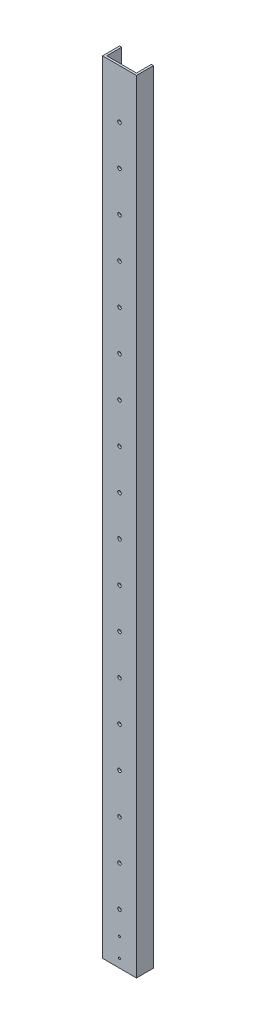
SolidWorks part; units mm, degrees
ref_plane "Front" through (0, 0, 0) normal (0, 0, 1) x (1, 0, 0)
ref_plane "Top" through (0, 0, 0) normal (0, 1, 0) x (1, 0, 0)
ref_plane "Right" through (0, 0, 0) normal (1, 0, 0) x (0, 0, -1)
sketch "Sketch1" plane through (0, 0, 0) normal (0, 1, 0) x (1, 0, 0)
  line L0 (3.175, 3.175) -> (3.175, 25.4)
  line L1 (0, 0) -> (50.8, 0)
  line L2 (0, 0) -> (0, 25.4)
  line L4 (50.8, 0) -> (50.8, 25.4)
  line L5 (3.175, 3.175) -> (47.625, 3.175)
  line L6 (47.625, 3.175) -> (47.625, 25.4)
  line L7 (0, 25.4) -> (3.175, 25.4)
  line L8 (50.8, 25.4) -> (47.625, 25.4)
  dimension "D1" = 25.4
  dimension "D2" = 50.8
  dimension "D3" = 3.175
extrude "Boss-Extrude1" add sketch "Sketch1" along normal blind 1168.4
sketch "Sketch2" plane through (0, 0, 0) normal (0, 0, 1) x (1, 0, 0)
  line L0 (25.4, 0) -> (25.4, 76.2) construction
  line L1 (0, 0) -> (50.8, 0) construction
  circle A0 centre (25.4, 76.2) radius 2.667
  circle A1 centre (25.4, 136.144) radius 2.667
  circle A2 centre (25.4, 196.088) radius 2.667
  circle A3 centre (25.4, 256.032) radius 2.667
  circle A4 centre (25.4, 315.976) radius 2.667
  circle A5 centre (25.4, 375.92) radius 2.667
  circle A6 centre (25.4, 435.864) radius 2.667
  circle A7 centre (25.4, 495.808) radius 2.667
  circle A8 centre (25.4, 555.752) radius 2.667
  circle A9 centre (25.4, 615.696) radius 2.667
  circle A10 centre (25.4, 675.64) radius 2.667
  circle A11 centre (25.4, 735.584) radius 2.667
  circle A12 centre (25.4, 795.528) radius 2.667
  circle A13 centre (25.4, 855.472) radius 2.667
  circle A14 centre (25.4, 915.416) radius 2.667
  circle A15 centre (25.4, 975.36) radius 2.667
  circle A16 centre (25.4, 1035.304) radius 2.667
  circle A17 centre (25.4, 1095.248) radius 2.667
  dimension "D2" = 5.334
  dimension "D1" = 76.2
  dimension "D3" = 18
extrude "Cut-Extrude1" cut sketch "Sketch2" against normal up to next
sketch "Sketch4" plane through (0, 0, 0) normal (0, 0, 1) x (1, 0, 0)
  line L0 (25.4, 41.275) -> (50.8, 41.275) construction
  line L1 (50.8, 1168.4) -> (50.8, 0) construction
  line L2 (25.4, 41.275) -> (0, 41.275) construction
  line L3 (0, 1168.4) -> (0, 0) construction
  line L4 (25.4, 41.275) -> (25.4, 12.7) construction
  line L5 (25.4, 12.7) -> (25.4, 0) construction
  line L6 (0, 0) -> (50.8, 0) construction
  circle A1 centre (25.4, 41.275) radius 1.5875
  circle A3 centre (25.4, 12.7) radius 1.5875
  dimension "D1" = 28.575
  dimension "D2" = 12.7
extrude "Cut-Extrude2" cut sketch "Sketch4" against normal up to next
ref_plane "Mid_Plane" through (25.4, 0, 0) normal (1, 0, 0) x (0, 0, -1)
